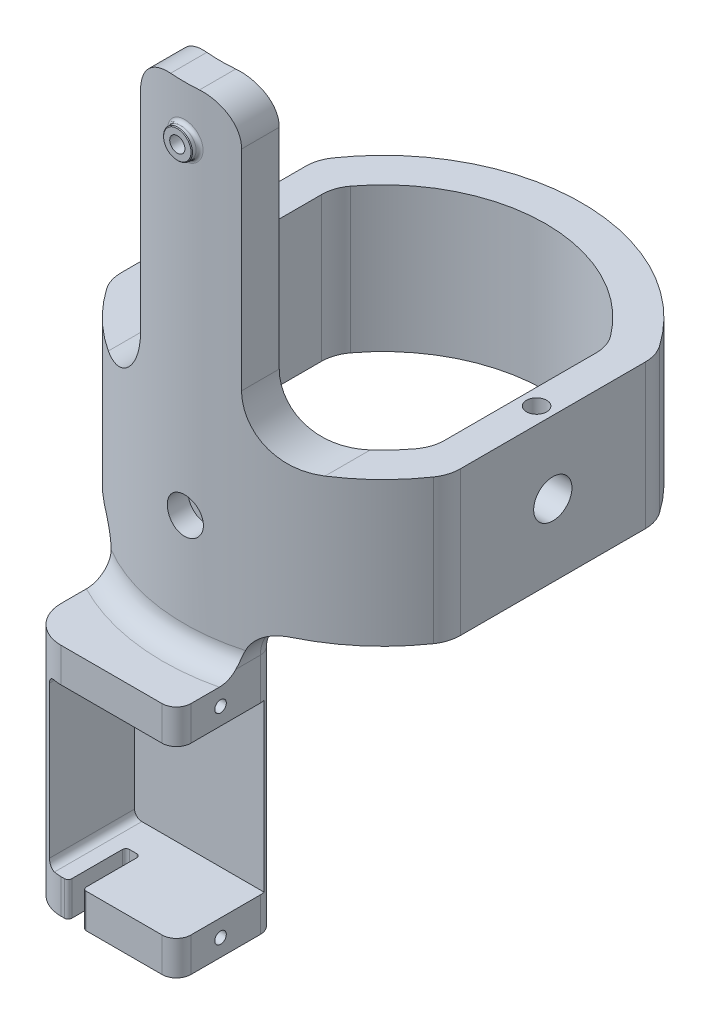
SolidWorks part; units mm, degrees
ref_plane "Plan de face" through (0, 0, 0) normal (0, 0, 1) x (1, 0, 0)
ref_plane "Plan de dessus" through (0, 0, 0) normal (0, 1, 0) x (1, 0, 0)
ref_plane "Plan de droite" through (0, 0, 0) normal (1, 0, 0) x (0, 0, -1)
sketch "Esquisse1" plane through (0, 0, 0) normal (0, 1, 0) x (1, 0, 0)
  line L0 (-23.5, 14.2829) -> (-23.5, -14.2829)
  line L1 (-19, 12.052) -> (-19, -12.052)
  line L2 (19, 12.052) -> (19, -12.052)
  line L3 (23.5, 14.2829) -> (23.5, -14.2829)
  arc A0 (-23.5, -14.2829) -> (23.5, -14.2829) centre (0, 0) ccw
  arc A2 (-19, -12.052) -> (19, -12.052) centre (0, 0) ccw
  arc A3 (19, 12.052) -> (-19, 12.052) centre (0, 0) ccw
  arc A4 (23.5, 14.2829) -> (-23.5, 14.2829) centre (0, 0) ccw
  dimension "D1" = 55
  dimension "D2" = 19
  dimension "D6" = 22.5
  dimension "D3" = 4.5
  dimension "D4" = 19
  dimension "D5" = 4.5
extrude "Boss.-Extru.1" add sketch "Esquisse1" along normal mid plane 20
ref_plane "Plan1" through (0, 0, 27.5) normal (0, 0, 1) x (1, 0, 0)
sketch "Esquisse3" plane through (0, 0, 27.5) normal (0, 0, 1) x (1, 0, 0)
  circle A0 centre (0, 0) radius 2.5
  dimension "D1" = 5
extrude "Enlèv. mat.-Extru.1" cut sketch "Esquisse3" against normal blind 3
mirror "Symétrie1" about plane through (0, 0, 0) normal (0, 0, 1) of "Enlèv. mat.-Extru.1"
sketch "Esquisse4" plane through (0, 10, 0) normal (0, 1, 0) x (1, 0, 0)
  line L0 (-7, -21.3834) -> (-7, -26.5942)
  line L1 (7, -21.3834) -> (7, -26.5942)
  arc A0 (-7, -26.5942) -> (7, -26.5942) centre (0, 0) ccw
  arc A1 (-7, -21.3834) -> (7, -21.3834) centre (0, 0) ccw
  arc A2 (-23.5, -14.2829) -> (23.5, -14.2829) centre (0, 0) ccw construction
  arc A3 (-19, -12.052) -> (19, -12.052) centre (0, 0) ccw construction
  dimension "D1" = 7
  dimension "D2" = 7
extrude "Boss.-Extru.2" add sketch "Esquisse4" along normal blind 42
sketch "Esquisse5" plane through (23.5, 0, 0) normal (1, 0, 0) x (0, 0, -1)
  circle A0 centre (0, 0) radius 2.65
  dimension "D1" = 5.3
extrude "Enlèv. mat.-Extru.2" cut sketch "Esquisse5" against normal up to next
mirror "Symétrie2" about plane through (0, 0, 0) normal (1, 0, 0) of "Enlèv. mat.-Extru.2"
ref_plane "Plan2" through (0, 0, 27.5) normal (0, 0, 1) x (1, 0, 0)
sketch "Esquisse6" plane through (0, 0, 27.5) normal (0, 0, 1) x (1, 0, 0)
  circle A0 centre (0, 45) radius 2
  dimension "D2" = 4
  dimension "D1" = 45
extrude "Boss.-Extru.3" add sketch "Esquisse6" along normal blind 1 and the other way blind 2
sketch "Esquisse13" plane through (0, 0, 28.5) normal (0, 0, 1) x (1, 0, 0)
  circle A0 centre (0, 45) radius 1.05
  dimension "D1" = 2.1
extrude "Enlèv. mat.-Extru.7" cut sketch "Esquisse13" against normal through all
sketch "Esquisse14" plane through (0, 0, 28.5) normal (0, 0, 1) x (1, 0, 0)
  circle A0 centre (0, 45) radius 2.5
  dimension "D1" = 5
extrude "Enlèv. mat.-Extru.8" cut sketch "Esquisse14" against normal through all from offset 3 offset against normal yes
sketch "Esquisse7" plane through (0, -10, 0) normal (0, -1, 0) x (1, 0, 0)
  line L0 (-14, 23.6696) -> (-14, 17.6139)
  line L1 (7, 26.5942) -> (7, 21.3834)
  line L2 (0, 0) -> (0, 13.7524) construction
  line L3 (7, 26.5942) -> (7, 21.3834) construction
  arc A0 (7, 21.3834) -> (-14, 17.6139) centre (0, 0) ccw
  arc A2 (7, 26.5942) -> (-14, 23.6696) centre (0, 0) ccw
  arc A3 (23.5, 14.2829) -> (-23.5, 14.2829) centre (0, 0) ccw construction
  arc A4 (19, 12.052) -> (-19, 12.052) centre (0, 0) ccw construction
  dimension "D1" = 14
extrude "Boss.-Extru.4" add sketch "Esquisse7" along normal blind 6
sketch "Esquisse8" plane through (0, -16, 0) normal (0, -1, 0) x (1, 0, 0)
  line L0 (-14, 17.6139) -> (-14, 35.6139)
  line L1 (7, 21.3834) -> (7, 35.6139)
  line L2 (-14, 35.6139) -> (7, 35.6139)
  line L3 (7, 21.3834) -> (7, 26.5942) construction
  line L4 (-14, 23.6696) -> (-14, 17.6139) construction
  arc A0 (7, 21.3834) -> (-14, 17.6139) centre (0, 0) ccw
  arc A3 (-14, 17.6139) -> (-19, 12.052) centre (0, 0) ccw construction
  dimension "D1" = 18
extrude "Boss.-Extru.5" add sketch "Esquisse8" along normal blind 32.5
sketch "Esquisse9" plane through (0, 0, 35.6139) normal (0, 0, 1) x (1, 0, 0)
  line L0 (7, -48.5) -> (7, -16) construction
  line L1 (7, -20.75) -> (-11, -20.75)
  line L2 (7, -20.75) -> (7, -43.75)
  line L3 (7, -43.75) -> (-11, -43.75)
  line L4 (-11, -20.75) -> (-11, -43.75)
  line L6 (7, -48.5) -> (-14, -48.5) construction
  dimension "D1" = 23
  dimension "D2" = 4.75
  dimension "D3" = 18
extrude "Enlèv. mat.-Extru.3" cut sketch "Esquisse9" against normal blind 12.2
sketch "Esquisse10" plane through (7, 0, 0) normal (1, 0, 0) x (0, 0, -1)
  circle A0 centre (-29.5139, -18.375) radius 0.8
  circle A1 centre (-29.5139, -46.125) radius 0.8
  circle A2 centre (-29.5139, -46.125) radius 0.75 construction
  dimension "D1" = 1.6
extrude "Enlèv. mat.-Extru.4" cut sketch "Esquisse10" against normal blind 5
fillet "Congé11" radius 2 4 edges at (7, -29.25, 21.3834) (7, -18.375, 35.6139) (7, -46.125, 35.6139) (-14, -29.25, 17.6139)
fillet "Congé5" radius 3 1 edges at (-3.7932, -16, 27.2371)
fillet "Congé6" radius 5 2 edges at (7, -10, 25.2893) (6.2617, -10, 22.4325)
fillet "Congé12" radius 3 2 edges at (-13.0102, -10, 19.6339) (-14, -10, 22.5148)
fillet "Congé1" radius 8 2 edges at (-7, 10, 23.9888) (7, 10, 23.9888)
fillet "Congé2" radius 5 2 edges at (7, 52, 23.9888) (-7, 52, 23.9888)
fillet "Congé4" radius 5 8 edges at (-19, 0, -12.052) (-19, 0, 12.052) (-23.5, 0, 14.2829) (-23.5, 0, -14.2829) (19, 0, -12.052) (19, 0, 12.052) (23.5, 0, 14.2829) (23.5, 0, -14.2829)
fillet "Congé7" radius 1 2 edges at (-11, -43.75, 29.5139) (-11, -20.75, 29.5139)
fillet "Congé8" radius 5 1 edges at (-14, -32.25, 35.6139)
sketch "Esquisse12" plane through (0, -48.5, 0) normal (0, -1, 0) x (1, 0, 0)
  line L0 (5, 35.6139) -> (-9, 35.6139) construction
  line L1 (-8, 35.6139) -> (-6, 35.6139)
  line L2 (-8, 35.6139) -> (-8, 27.6139)
  line L3 (-8, 27.6139) -> (-6, 27.6139)
  line L4 (-6, 35.6139) -> (-6, 27.6139)
  line L6 (-9.5, 35.6139) -> (-9.5, 23.4139) construction
  dimension "D2" = 2
  dimension "D3" = 1.5
  dimension "D4" = 8
extrude "Enlèv. mat.-Extru.6" cut sketch "Esquisse12" against normal up to next
fillet "Congé13" radius 0.5 4 edges at (-6, -46.125, 27.6139) (-8, -46.125, 27.6139) (-6, -46.125, 35.6139) (-8, -46.125, 35.6139)
fillet "Congé14" radius 0.5 1 edges at (-1.9478, 45.4541, 27.4309)
chamfer "Chanfrein1" distance 0.1 angle 45 1 edges at (2, 45, 28.5)
sketch "Esquisse15" plane through (0, 10, 0) normal (0, 1, 0) x (1, 0, 0)
  line L0 (-23.5, 2.65) -> (-19, -2.65) construction
  line L1 (19, 2.65) -> (23.5, -2.65) construction
  circle A0 centre (-21.25, 0) radius 1.4
  circle A1 centre (21.25, 0) radius 1.4
  dimension "D1" = 2.8
extrude "Enlèv. mat.-Extru.9" cut sketch "Esquisse15" against normal up to next
